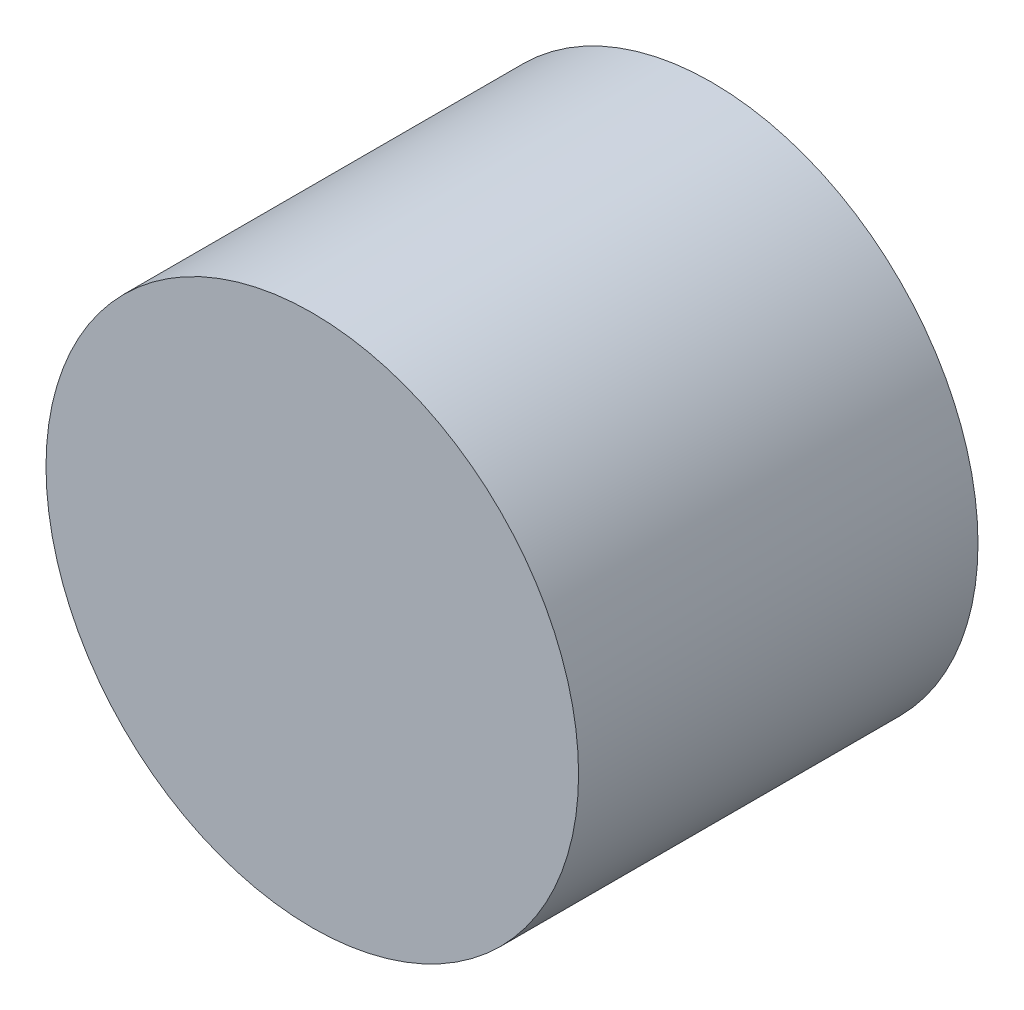
SolidWorks part; units mm, degrees
ref_plane "前视基准面" through (0, 0, 0) normal (0, 0, 1) x (1, 0, 0)
ref_plane "上视基准面" through (0, 0, 0) normal (0, 1, 0) x (1, 0, 0)
ref_plane "右视基准面" through (0, 0, 0) normal (1, 0, 0) x (0, 0, -1)
ref_axis "基准轴1" through (0, 0, 55) along (0, 0, -1)
sketch "SketchRevolveGearBelt01" plane through (0, 0, 0) normal (1, 0, 0) x (0, 0, -1)
  line L0 (0, 0) -> (1, 0) construction
  line L1 (6.4008, 0) -> (6.4008, 6.1455)
  line L2 (6.4008, 6.1455) -> (5.6388, 6.1455)
  line L3 (5.6388, 6.1455) -> (5.6388, 7.0099)
  line L4 (5.6388, 7.0099) -> (6.2015, 8.3685)
  line L5 (6.2015, 8.3685) -> (5.4975, 8.6601)
  line L6 (5.4975, 8.6601) -> (4.8768, 7.1615)
  line L7 (4.8768, 7.1615) -> (4.8768, 6.7805)
  line L8 (4.8768, 6.7805) -> (-4.8768, 6.7805)
  line L9 (-4.8768, 6.7805) -> (-4.8768, 7.1615)
  line L10 (-4.8768, 7.1615) -> (-5.4975, 8.6601)
  line L11 (-5.4975, 8.6601) -> (-6.2015, 8.3685)
  line L12 (-6.2015, 8.3685) -> (-5.6388, 7.0099)
  line L13 (-5.6388, 7.0099) -> (-5.6388, 6.1455)
  line L14 (-5.6388, 6.1455) -> (-6.4008, 6.1455)
  line L15 (-6.4008, 6.1455) -> (-6.4008, 0)
  line L16 (-6.4008, 0) -> (6.4008, 0)
  dimension "GearBeltFlange1OutsideLength" = 0.8644
  dimension "GearBeltFlange1X" = 0.5627
  dimension "GearBeltFlange1Y" = 1.3586
  dimension "GearBeltFlangeThickness" = 0.762
  dimension "GearBeltFlangeInside" = 0.381
  dimension "GearBeltOutsideDiameter" = 6.7805
  dimension "GearBeltFlange2X" = 0.5627
revolve "GearBelt01" add sketch "SketchRevolveGearBelt01" angle 360 about L0
sketch "SketchToothGearBelt01" plane through (0, 0, 0) normal (0, 0, 1) x (1, 0, 0)
  arc A0 (6.6611, 1.2728) -> (6.6611, -1.2728) centre (0, 0) cw
  spline S0 degree 3 poles (6.6611, -1.2728) (6.6636, -1.2597) (6.6656, -1.2396) (6.6648, -1.2127) (6.6624, -1.1927) (6.6583, -1.173) (6.6525, -1.1538) (6.645, -1.1351) (6.6358, -1.1171) (6.6252, -1.1) (6.6131, -1.084) (6.5996, -1.069) (6.5848, -1.0553) (6.569, -1.0429) (6.552, -1.032) (6.5342, -1.0226) (6.5157, -1.0148) (6.4965, -1.0087) (6.4769, -1.0041) (6.4278, -0.9983) (6.3619, -0.9935) (6.281, -0.9768) (6.2139, -0.9578) (6.1485, -0.9335) (6.0852, -0.9041) (6.0244, -0.8699) (5.9665, -0.8311) (5.9117, -0.7878) (5.8606, -0.7404) (5.8133, -0.6891) (5.7702, -0.6343) (5.7315, -0.5762) (5.6975, -0.5154) (5.6683, -0.452) (5.6442, -0.3865) (5.6253, -0.3194) (5.6117, -0.251) (5.6034, -0.1817) (5.6014, -0.1166) (5.6018, -0.056) (5.6017, 0) (5.6018, 0.056) (5.6014, 0.1166) (5.6034, 0.1817) (5.6117, 0.251) (5.6253, 0.3194) (5.6442, 0.3865) (5.6683, 0.452) (5.6975, 0.5154) (5.7315, 0.5762) (5.7702, 0.6343) (5.8133, 0.6891) (5.8606, 0.7404) (5.9117, 0.7878) (5.9665, 0.8311) (6.0244, 0.8699) (6.0852, 0.9041) (6.1485, 0.9335) (6.2139, 0.9578) (6.281, 0.9768) (6.3619, 0.9935) (6.4278, 0.9983) (6.4769, 1.0041) (6.4965, 1.0087) (6.5157, 1.0148) (6.5342, 1.0226) (6.552, 1.032) (6.569, 1.0429) (6.5848, 1.0553) (6.5996, 1.069) (6.6131, 1.084) (6.6252, 1.1) (6.6358, 1.1171) (6.645, 1.1351) (6.6525, 1.1538) (6.6583, 1.173) (6.6624, 1.1927) (6.6648, 1.2127) (6.6656, 1.2396) (6.6636, 1.2597) (6.6611, 1.2728) knots 0 0 0 0 0.010832 0.016248 0.021665 0.027081 0.032497 0.037913 0.043329 0.048745 0.054162 0.059578 0.064994 0.07041 0.075826 0.081242 0.086659 0.092075 0.097491 0.102907 0.132017 0.150785 0.169553 0.18832 0.207088 0.225855 0.244623 0.263391 0.282158 0.300926 0.319694 0.338461 0.357229 0.375997 0.394764 0.413532 0.4323 0.451067 0.469835 0.484917 0.5 0.515083 0.530165 0.548933 0.5677 0.586468 0.605236 0.624003 0.642771 0.661539 0.680306 0.699074 0.717842 0.736609 0.755377 0.774145 0.792912 0.81168 0.830447 0.849215 0.867983 0.897093 0.902509 0.907925 0.913341 0.918758 0.924174 0.92959 0.935006 0.940422 0.945838 0.951255 0.956671 0.962087 0.967503 0.972919 0.978335 0.983752 0.989168 1 1 1 1
extrude "ToothExtrudeCutGearBelt01" cut sketch "SketchToothGearBelt01" against normal blind 4.8768 and the other way blind 4.8768
pattern_circular "PatternGearBelt01" count 15 every 24 about axis through (0, 0, 55) along (0, 0, -1) of "ToothExtrudeCutGearBelt01"
sketch "BoreRevolveSketch" plane through (0, 0, 0) normal (1, 0, 0) x (0, 0, -1)
  line L0 (0, 0) -> (1, 0) construction
  line L1 (-6.4008, 0) -> (6.4008, 0)
  line L2 (6.4008, 0) -> (6.4008, 3)
  line L3 (6.4008, 3) -> (-6.4008, 3)
  line L4 (-6.4008, 3) -> (-6.4008, 0)
  dimension "TaperSide1" = 3
  dimension "TaperSide2" = 3
revolve "BoreRevolveCut" cut sketch "BoreRevolveSketch" angle 360 about L0
sketch "AuxiliarySketchGearBelt01" plane through (0, 0, 0) normal (0, 0, 1) x (1, 0, 0)
  circle A0 centre (0, 0) radius 7.1615 construction
  dimension "PitchDiameter" = 14.3229
sketch "草图1" plane through (0, 0, -6.4008) normal (0, 0, -1) x (-1, 0, 0)
  circle A0 centre (0, 0) radius 10
extrude "凸台-拉伸1" add sketch "草图1" against normal blind 15
